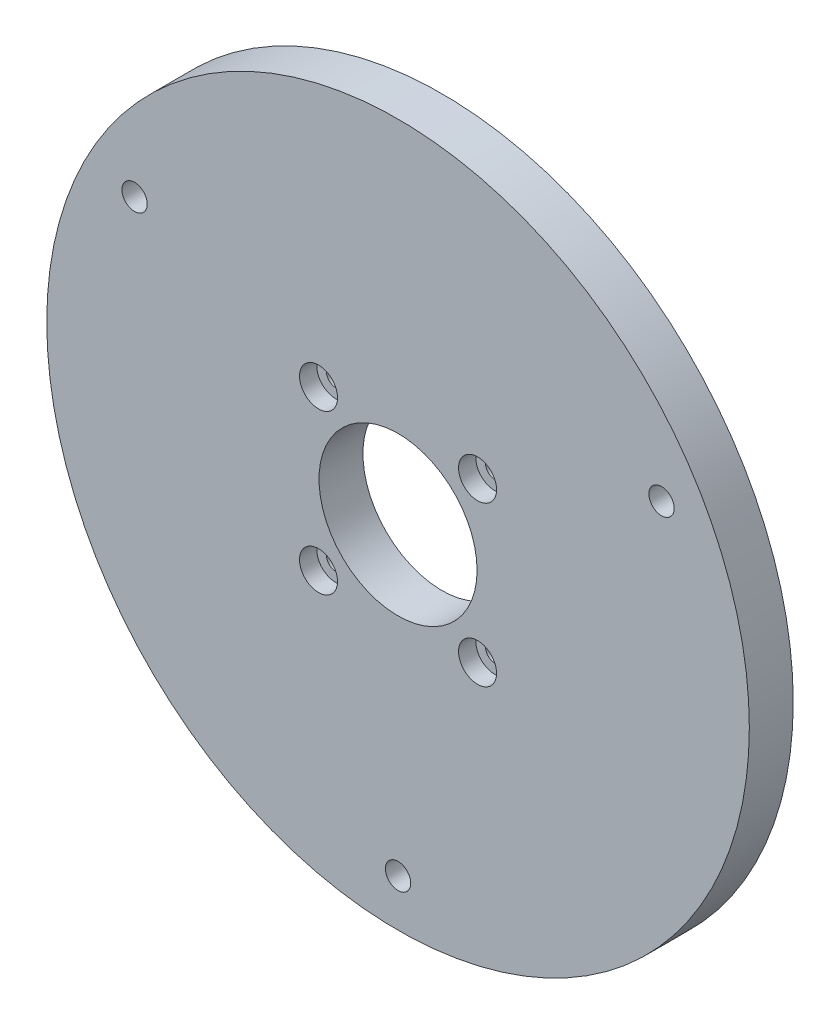
SolidWorks part; units mm, degrees
material "Acrylic (Medium-high impact)"
ref_plane "Front Plane" through (0, 0, 0) normal (0, 0, 1) x (1, 0, 0)
ref_plane "Top Plane" through (0, 0, 0) normal (0, 1, 0) x (1, 0, 0)
ref_plane "Right Plane" through (0, 0, 0) normal (1, 0, 0) x (0, 0, -1)
sketch "Sketch1" plane through (0, 0, 0) normal (0, 0, 1) x (1, 0, 0)
  circle A0 centre (0, 0) radius 50.8
  dimension "D1" = 101.6
extrude "Boss-Extrude1" add sketch "Sketch1" along normal blind 6.35
sketch "Sketch2" plane through (0, 0, 6.35) normal (0, 0, 1) x (1, 0, 0)
  circle A0 centre (0, 0) radius 11.43
  dimension "D1" = 22.86
extrude "Cut-Extrude1" cut sketch "Sketch2" against normal through all
hole_wizard "CBORE for M2.5 SHCS1" positions "Sketch3" profile "Sketch5" counterbore size "M2.5" standard "ANSI Metric"
sketch "Sketch3" plane through (0, 0, 6.35) normal (0, 0, 1) x (1, 0, 0)
  line L1 (-11.5, -11.5) -> (11.5, -11.5)
  line L2 (-11.5, -11.5) -> (-11.5, 11.5)
  line L3 (-11.5, 11.5) -> (11.5, 11.5)
  line L4 (11.5, -11.5) -> (11.5, 11.5)
  line L5 (-11.5, -11.5) -> (11.5, 11.5) construction
  line L6 (-11.5, 11.5) -> (11.5, -11.5) construction
  point P1 (0, 0)
  point P2 (11.5, 11.5)
  point P59 (-11.5, -11.5)
  point P60 (-11.5, 11.5)
  point P61 (11.5, -11.5)
  dimension "D1" = 23
sketch "Sketch5" plane through (0, 0, 6.35) normal (1, 0, 0) x (0, -1, 0)
  line L0 (0, 0) -> (0, 10.9712)
  line L1 (0, 10.9712) -> (1.35, 10.16)
  line L2 (1.35, 10.16) -> (1.35, 2.5)
  line L3 (1.35, 2.5) -> (2.75, 2.5)
  line L4 (2.75, 2.5) -> (2.75, 0)
  line L5 (2.75, 0) -> (0, 0)
  line L10 (0, 10.9712) -> (-1.35, 10.16) construction
  line L11 (0, -6.35) -> (0, 107.95) construction
  dimension "Hole Dia." = 2.7
  dimension "Hole Depth" = 10.16
  dimension "C'Bore Dia." = 5.5
  dimension "C'Bore Depth" = 2.5
  dimension "Drill Angle" = 118
hole_wizard "#6 Clearance Hole1" positions "Sketch7" profile "Sketch9" hole size "#6" standard "ANSI Inch"
sketch "Sketch7" plane through (0, 0, 6.35) normal (0, 0, 1) x (1, 0, 0)
  line L1 (0, -43.9941) -> (38.1, 21.997)
  line L2 (38.1, 21.997) -> (-38.1, 21.997)
  line L3 (-38.1, 21.997) -> (0, -43.9941)
  line L8 (-11.5, 11.5) -> (11.5, 11.5) construction
  circle A0 centre (0, 0) radius 21.997 construction
  point P3 (0, -43.9941)
  point P4 (38.1, 21.997)
  point P5 (-38.1, 21.997)
  dimension "D1" = 76.2
sketch "Sketch9" plane through (-38.1, 21.997, 6.35) normal (1, 0, 0) x (0, -1, 0)
  line L0 (0, 0) -> (0, 11.2589)
  line L1 (0, 11.2589) -> (1.8288, 10.16)
  line L2 (1.8288, 10.16) -> (1.8288, 0)
  line L5 (1.8288, 0) -> (0, 0)
  line L10 (0, 11.2589) -> (-1.8288, 10.16) construction
  line L11 (0, -6.35) -> (0, 107.95) construction
  dimension "Hole Dia." = 3.6576
  dimension "Hole Depth" = 10.16
  dimension "Drill Angle" = 118
fillet "Fillet1" [suppressed] radius 0.508
